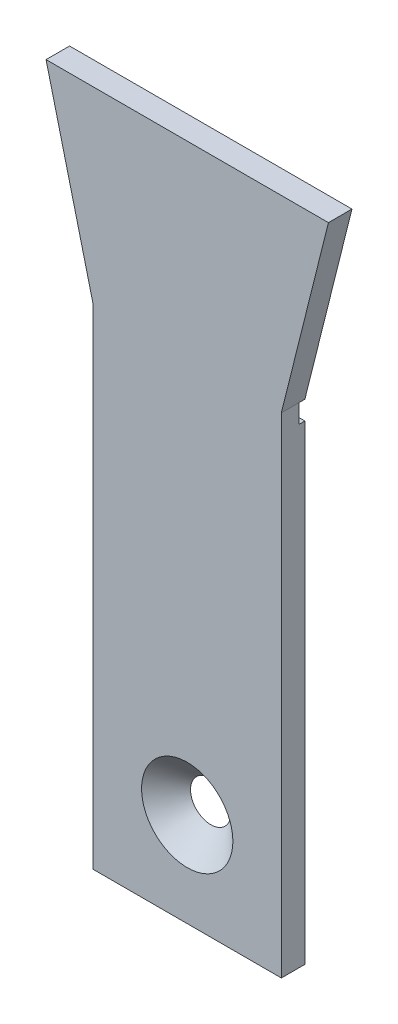
SolidWorks part; units mm, degrees
ref_plane "Płaszczyzna przednia" through (0, 0, 0) normal (0, 0, 1) x (1, 0, 0)
ref_plane "Płaszczyzna górna" through (0, 0, 0) normal (0, 1, 0) x (1, 0, 0)
ref_plane "Płaszczyzna prawa" through (0, 0, 0) normal (1, 0, 0) x (0, 0, -1)
sketch "Szkic1" plane through (0, 0, 0) normal (0, 0, 1) x (1, 0, 0)
  line L0 (-10, 0) -> (10, 0)
  line L1 (10, 0) -> (10, 50)
  line L2 (10, 50) -> (10, 52)
  line L3 (10, 52) -> (15, 72)
  line L4 (15, 72) -> (-15, 72)
  line L5 (-15, 72) -> (-10, 52)
  line L6 (-10, 52) -> (-10, 50)
  line L7 (-10, 50) -> (-10, 0)
  point P2 (0, 0)
  point P9 (0, 72)
  dimension "D1" = 20
  dimension "D2" = 20
  dimension "D3" = 2
  dimension "D4" = 50
  dimension "D5" = 30
sketch "Szkic2" plane through (0, 0, 0) normal (0, 0, 1) x (1, 0, 0)
  line L1 (-10, 52) -> (10, 52)
  line L2 (-10, 52) -> (-10, 50)
  line L3 (-10, 50) -> (10, 50)
  line L4 (10, 52) -> (10, 50)
extrude "Dodanie-wyciągnięcie1" add sketch "Szkic1" along normal blind 2.5
extrude "Wytnij-wyciągnięcie1" cut sketch "Szkic2" along normal blind 0.6
sketch "Szkic3" plane through (0, 0, 2.5) normal (0, 0, 1) x (1, 0, 0)
  line L0 (0, -1.375) -> (0, 1.375) construction
  line L1 (-10, 0) -> (10, 0) construction
  circle A0 centre (0, 10) radius 2.15
  dimension "D1" = 4.3
  dimension "D2" = 10
extrude "Wytnij-wyciągnięcie2" cut sketch "Szkic3" against normal through all
chamfer "Sfazowanie1" distance 2.7 distance2 2.5 1 edges at (2.15, 10, 2.5) first distance on face at (2.15, 10, 2.5)
